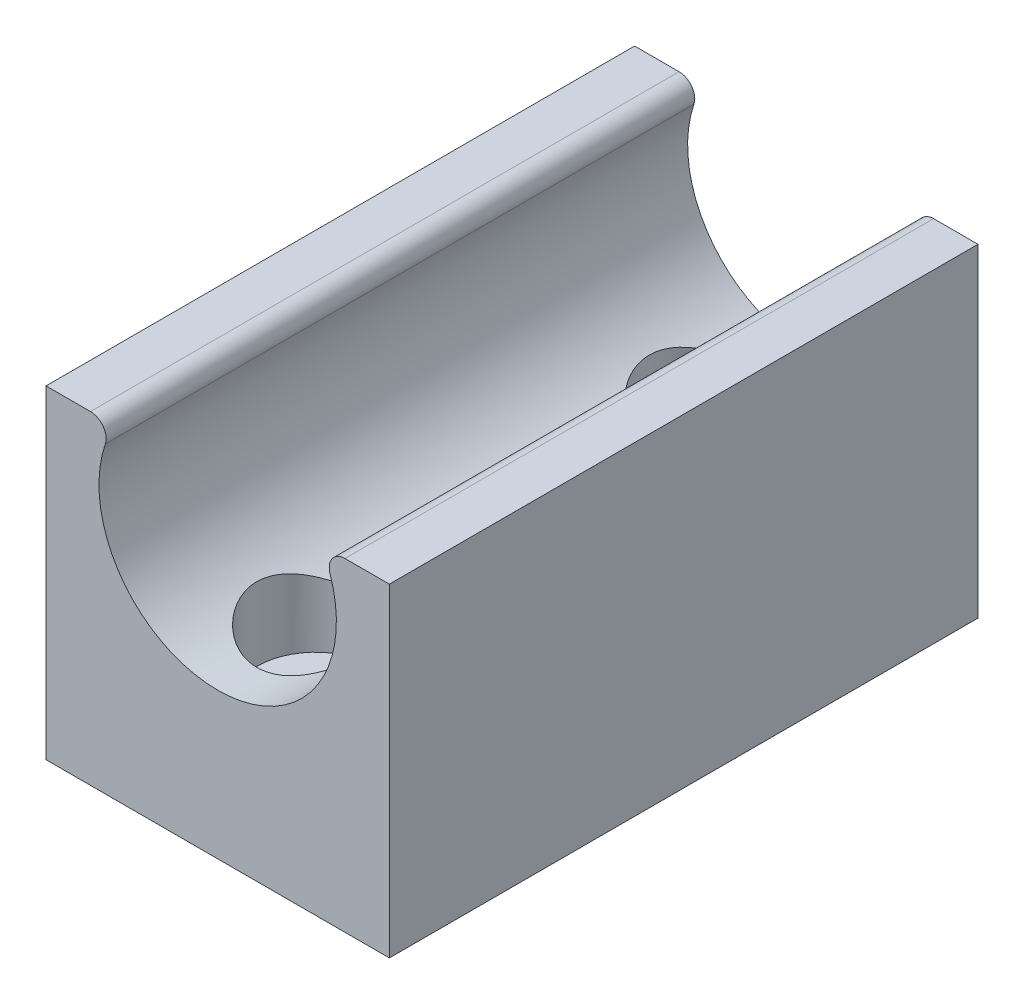
SolidWorks part; units mm, degrees
ref_plane "Front Plane" through (0, 0, 0) normal (0, 0, 1) x (1, 0, 0)
ref_plane "Top Plane" through (0, 0, 0) normal (0, 1, 0) x (1, 0, 0)
ref_plane "Right Plane" through (0, 0, 0) normal (1, 0, 0) x (0, 0, -1)
sketch "Sketch1" plane through (0, 0, 0) normal (0, 0, 1) x (1, 0, 0)
  line L0 (-5.25, 8.25) -> (-8.75, 8.25)
  line L1 (8.75, -8.25) -> (-8.75, -8.25)
  line L2 (8.75, -8.25) -> (8.75, 8.25)
  line L3 (8.75, 8.25) -> (5.25, 8.25)
  line L4 (-8.75, -8.25) -> (-8.75, 8.25)
  line L5 (8.75, -8.25) -> (-8.75, 8.25) construction
  line L6 (8.75, 8.25) -> (-8.75, -8.25) construction
  arc A0 (-5.25, 8.25) -> (5.25, 8.25) centre (0, 5.2433) ccw
  point P0 (0, 0)
  dimension "D1" = 12.1
  dimension "D2" = 3.5
  dimension "D3" = 17.5
  dimension "D4" = 16.5
extrude "Boss-Extrude1" add sketch "Sketch1" along normal blind 30
fillet "Fillet1" radius 0.8 2 edges at (5.25, 8.25, 15) (-5.25, 8.25, 15)
sketch "Sketch3" plane through (0, 8.25, 0) normal (0, 1, 0) x (1, 0, 0)
  line L0 (6.05, 0) -> (-6.05, 0) construction
  line L1 (-6.05, -30) -> (6.05, -30) construction
  circle A0 centre (0, -5) radius 3
  circle A1 centre (0, -25) radius 3
  dimension "D1" = 6
  dimension "D2" = 5
  dimension "D3" = 5
extrude "Cut-Extrude1" cut sketch "Sketch3" against normal blind 12
sketch "Sketch4" plane through (0, 8.25, 0) normal (0, 1, 0) x (1, 0, 0)
  circle A0 centre (0, -5) radius 1.55
  circle A1 centre (0, -25) radius 1.55
  dimension "D1" = 3.1
  dimension "D2" = 3.1
extrude "Cut-Extrude2" cut sketch "Sketch4" against normal through all
